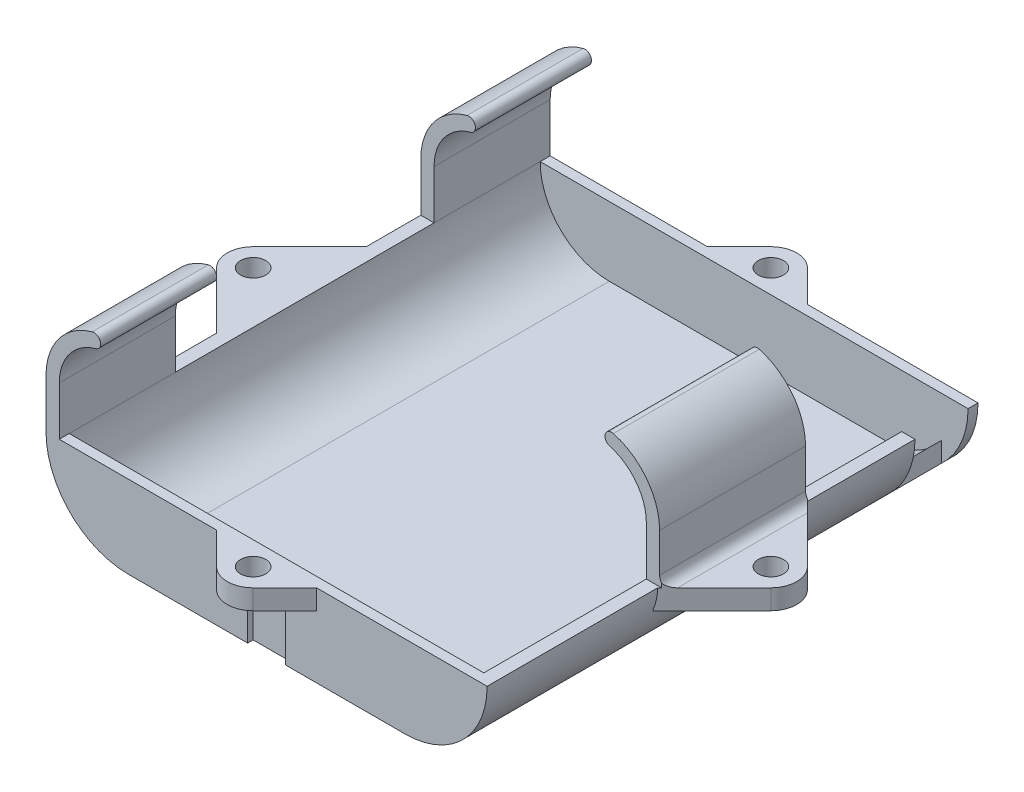
SolidWorks part; units mm, degrees
material "ABS"
ref_plane "Front Plane" through (0, 0, 0) normal (0, 0, 1) x (1, 0, 0)
ref_plane "Top Plane" through (0, 0, 0) normal (0, 1, 0) x (1, 0, 0)
ref_plane "Right Plane" through (0, 0, 0) normal (1, 0, 0) x (0, 0, -1)
sketch "Sketch1" plane through (0, 0, 0) normal (0, 0, 1) x (1, 0, 0)
  line L1 (0, 0) -> (62.5, 0) construction
  line L2 (0, 0) -> (0, 20.8333) construction
  line L3 (0, 20.8333) -> (62.5, 20.8333) construction
  line L4 (62.5, 0) -> (62.5, 20.8333) construction
  circle A0 centre (31.25, 10.4167) radius 10.4167
  circle A1 centre (10.4167, 10.4167) radius 10.4167
  circle A2 centre (52.0833, 10.4167) radius 10.4167
  arc A3 (23.8843, 17.7824) -> (17.7824, 17.7824) centre (20.8333, 20.8333) cw
  arc A4 (38.6157, 17.7824) -> (44.7176, 17.7824) centre (41.6667, 20.8333) ccw
  arc A5 (17.7824, 3.051) -> (23.8843, 3.051) centre (20.8333, 0) cw
  arc A6 (38.6157, 3.051) -> (44.7176, 3.051) centre (41.6667, 0) cw
  point P8 (31.25, 20.8333)
  dimension "D2" = 62.5
extrude "Boss-Extrude1" add sketch "Sketch1" along normal blind 65 contours A1 | A0 A3 A1 | A1 A5 A0 | A0 | A0 A6 A2 | A4 A0 A2 | A2 region at (31.25, 10.4167, 0) region at (41.6667, 5.6133, 0) region at (41.6667, 15.22, 0) region at (52.0833, 10.4167, 0) region at (20.8333, 15.22, 0) region at (20.8333, 5.6133, 0) region at (10.4167, 10.4167, 0)
fillet "Fillet1" radius 2 16 edges at (31.25, 0, 0) (41.6667, 4.3147, 0) (62.5, 10.4167, 0) (41.6667, 16.5186, 0) (31.25, 20.8333, 0) (20.8333, 16.5186, 0) (0, 10.4167, 0) (20.8333, 4.3147, 0) (0, 10.4167, 65) (20.8333, 16.5186, 65) (31.25, 20.8333, 65) (41.6667, 16.5186, 65) (62.5, 10.4167, 65) (41.6667, 4.3147, 65) (31.25, 0, 65) (20.8333, 4.3147, 65)
sketch "Sketch2" plane through (0, 0, 0) normal (0, 0, -1) x (-1, 0, 0)
  line L3 (-52.0833, 0) -> (-10.4167, 0)
  line L4 (-52.0833, -2) -> (-10.4167, -2)
  line L5 (-62.5, 10.4167) -> (-64.5, 10.4167)
  line L6 (0, 10.4167) -> (2, 10.4167)
  arc A0 (-44.7176, 17.7824) -> (-44.7176, 3.051) centre (-52.0833, 10.4167) ccw construction
  arc A1 (-17.7824, 3.051) -> (-17.7824, 17.7824) centre (-10.4167, 10.4167) ccw construction
  arc A5 (-62.5, 10.4167) -> (-52.0833, 0) centre (-52.0833, 10.4167) ccw
  arc A9 (-10.4167, 0) -> (0, 10.4167) centre (-10.4167, 10.4167) ccw
  arc A15 (-64.5, 10.4167) -> (-52.0833, -2) centre (-52.0833, 10.4167) ccw
  arc A16 (-10.4167, -2) -> (2, 10.4167) centre (-10.4167, 10.4167) ccw
  dimension "D1" = 2
extrude "Boss-Extrude2" add sketch "Sketch2" against normal blind 74 separate body
sketch "Sketch3" plane through (0, 10.4167, 0) normal (0, 1, 0) x (1, 0, 0)
  line L0 (64.5, -74) -> (64.5, 0) construction
  line L1 (-2, 0) -> (64.5, 0)
  line L2 (-2, 0) -> (-2, -1.5)
  line L3 (-2, -1.5) -> (64.5, -1.5)
  line L4 (64.5, 0) -> (64.5, -1.5)
  line L6 (-2, -74) -> (64.5, -74)
  line L7 (-2, -74) -> (-2, -72.5)
  line L8 (-2, -72.5) -> (64.5, -72.5)
  line L9 (64.5, -74) -> (64.5, -72.5)
  dimension "D1" = 1.5
  dimension "D2" = 1.5
extrude "Boss-Extrude3" add sketch "Sketch3" against normal up to next
sketch "Sketch4" plane through (0, 10.4167, 0) normal (0, 1, 0) x (1, 0, 0)
  line L0 (31.25, 0) -> (31.25, -74) construction
  line L1 (-2, 0) -> (64.5, 0) construction
  line L2 (-2, -74) -> (64.5, -74) construction
  line L3 (-2, -37) -> (64.5, -37) construction
  line L4 (-2, -74) -> (-2, 0) construction
  line L5 (64.5, -74) -> (64.5, 0) construction
  line L6 (28.4923, 4.7777) -> (22.2146, -1.5)
  line L7 (0, -1.5) -> (62.5, -1.5) construction
  line L8 (22.2146, -1.5) -> (40.2854, -1.5)
  line L9 (52.0833, -1.5) -> (10.4167, -1.5) construction
  line L10 (40.2854, -1.5) -> (34.0077, 4.7777)
  line L11 (73.0277, -34.2423) -> (62.5, -23.7146)
  line L12 (62.5, -72.5) -> (62.5, -1.5) construction
  line L13 (62.5, -23.7146) -> (62.5, -50.2854)
  line L14 (62.5, -50.2854) -> (73.0277, -39.7577)
  line L15 (0, -23.7146) -> (0, -50.2854)
  line L16 (-10.5277, -34.2423) -> (0, -23.7146)
  line L17 (0, -50.2854) -> (-10.5277, -39.7577)
  line L18 (22.2146, -72.5) -> (40.2854, -72.5)
  line L19 (28.4923, -78.7777) -> (22.2146, -72.5)
  line L20 (40.2854, -72.5) -> (34.0077, -78.7777)
  circle A0 centre (31.25, 2.02) radius 1.9
  arc A1 (28.4923, 4.7777) -> (34.0077, 4.7777) centre (31.25, 2.02) cw
  circle A2 centre (70.27, -37) radius 1.9
  arc A3 (73.0277, -34.2423) -> (73.0277, -39.7577) centre (70.27, -37) cw
  circle A4 centre (-7.77, -37) radius 1.9
  arc A5 (-10.5277, -34.2423) -> (-10.5277, -39.7577) centre (-7.77, -37) ccw
  circle A6 centre (31.25, -76.02) radius 1.9
  arc A7 (28.4923, -78.7777) -> (34.0077, -78.7777) centre (31.25, -76.02) ccw
  dimension "D1" = 3.8
  dimension "D3" = 2
  dimension "D4" = 3.8
  dimension "D5" = 2
  dimension "D2" = 2.02
  dimension "D6" = 5.77
  dimension "D7" = 45
  dimension "D8" = 45
extrude "Boss-Extrude4" add sketch "Sketch4" against normal blind 3
sketch "Sketch5" plane through (0, 10.4167, 0) normal (0, 1, 0) x (1, 0, 0)
  line L0 (64.5, -25.7146) -> (64.5, 0) construction
  line L1 (64.5, -1.5) -> (60.5, -1.5)
  line L2 (64.5, -1.5) -> (64.5, -9.5)
  line L3 (64.5, -9.5) -> (60.5, -9.5)
  line L4 (60.5, -1.5) -> (60.5, -9.5)
  line L5 (52.0833, -1.5) -> (62.5, -1.5) construction
  dimension "D1" = 8
  dimension "D2" = 4
extrude "Cut-Extrude1" cut sketch "Sketch5" against normal blind 10
sketch "Sketch6" plane through (0, 0, 74) normal (0, 0, 1) x (1, 0, 0)
  line L0 (64.5, 10.4167) -> (62.5, 10.4167)
  line L1 (38.7854, 10.4167) -> (64.5, 10.4167) construction
  line L2 (62.5, 10.4167) -> (62.5, 17.7716)
  line L3 (31.25, 10.4167) -> (31.25, 23.9435) construction
  line L4 (34.0077, 10.4167) -> (28.4923, 10.4167) construction
  line L6 (64.5, 12.4167) -> (64.5, 17.7716)
  line L7 (64.5, 12.4167) -> (64.5, 12.4167) construction
  line L8 (64.5, 10.4167) -> (64.5, 12.4167)
  line L9 (-2, 10.4167) -> (0, 10.4167)
  line L10 (0, 10.4167) -> (0, 17.7716)
  line L11 (-2, 12.4167) -> (-2, 17.7716)
  line L12 (-2, 10.4167) -> (-2, 12.4167)
  arc A0 (62.5, 17.7716) -> (57, 25) centre (55, 17.7716) ccw
  arc A1 (64.5, 17.7716) -> (57.5333, 26.9276) centre (55, 17.7716) ccw
  arc A3 (57, 25) -> (57.5333, 26.9276) centre (57.2667, 25.9638) cw
  arc A4 (0, 17.7716) -> (5.5, 25) centre (7.5, 17.7716) cw
  arc A5 (5.5, 25) -> (4.9667, 26.9276) centre (5.2333, 25.9638) ccw
  arc A6 (-2, 17.7716) -> (4.9667, 26.9276) centre (7.5, 17.7716) cw
  line M18 (23.7146, 10.4167) -> (-2, 10.4167)
  line M22 (64.5, 10.4167) -> (38.7854, 10.4167)
  dimension "D3" = 7.5
  dimension "D1" = 25
  dimension "D2" = 2
  dimension "D4" = 2
extrude "Boss-Extrude5" add sketch "Sketch6" against normal blind 22 from offset 26 contours A3 A0 L2 L8 L6 A1 M22 region at (63.5, 10.6015, 74) offset against normal yes
extrude "Boss-Extrude6" add sketch "Sketch6<3>" against normal blind 17.5 contours A6 L11 L12 L10 A4 A5 M18 region at (-1.8152, 11.4167, 74)
sketch "Sketch6<3>" plane through (0, 0, 74) normal (0, 0, 1) x (1, 0, 0) same geometry as "Sketch6"
ref_plane "Plane1" through (0, 0, 37) normal (0, 0, 1) x (1, 0, 0)
mirror "Mirror1" about plane through (0, 0, 37) normal (0, 0, 1) of "Boss-Extrude6"
fillet "Fillet2" radius 1.5 1 edges at (64.5, 10.4167, 37)
delete or keep bodies "Body-Delete/Keep 1" type delete bodies bodies 101
sketch "Sketch8" plane through (0, -2, 0) normal (0, -1, 0) x (1, 0, 0)
  line L1 (28.4, 0) -> (34.1, 0)
  line L2 (28.4, 0) -> (28.4, 0.83)
  line L3 (28.4, 0.83) -> (34.1, 0.83)
  line L4 (34.1, 0) -> (34.1, 0.83)
  line L5 (10.4167, 37) -> (52.0833, 37) construction
  line L6 (10.4167, 74) -> (10.4167, 0) construction
  line L7 (52.0833, 74) -> (52.0833, 0) construction
  line L8 (28.4, 73.17) -> (34.1, 73.17)
  line L9 (34.1, 74) -> (34.1, 73.17)
  line L10 (28.4, 74) -> (34.1, 74)
  line L11 (28.4, 74) -> (28.4, 73.17)
  line L13 (52.0833, 0) -> (10.4167, 0) construction
  circle A0 centre (31.25, -2.02) radius 1.9 construction
  point P20 (31.25, 0)
  dimension "D1" = 2.85
  dimension "D2" = 5.7
extrude "Cut-Extrude4" cut sketch "Sketch8" against normal up to surface (9.4167 mm away) up to face at (29.35, 7.4167, -2.02)
